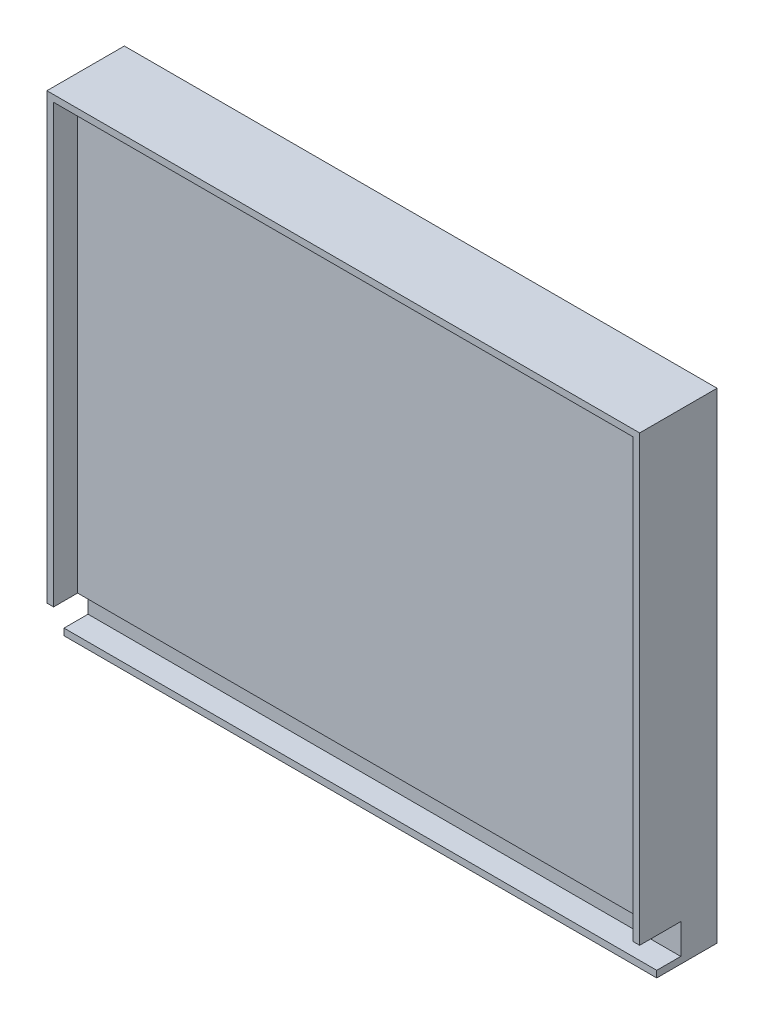
SolidWorks part; units mm, degrees
ref_plane "Front Plane" through (0, 0, 0) normal (0, 0, 1) x (1, 0, 0)
ref_plane "Top Plane" through (0, 0, 0) normal (0, 1, 0) x (1, 0, 0)
ref_plane "Right Plane" through (0, 0, 0) normal (1, 0, 0) x (0, 0, -1)
sketch "Sketch1" plane through (0, 0, 0) normal (0, 0, 1) x (1, 0, 0)
  line L1 (-68.3632, 130.6396) -> (213.5768, 130.6396)
  line L2 (-68.3632, 130.6396) -> (-68.3632, -97.9604)
  line L3 (-68.3632, -97.9604) -> (213.5768, -97.9604)
  line L4 (213.5768, 130.6396) -> (213.5768, -97.9604)
  dimension "D1" = 281.94
  dimension "D2" = 228.6
extrude "Boss-Extrude2" add sketch "Sketch1" along normal blind 25.4
sketch "Sketch3" plane through (0, 0, 25.4) normal (0, 0, 1) x (1, 0, 0)
  line L0 (-68.3632, -97.9604) -> (-68.3632, -80.4344)
  line L1 (-68.3632, 130.6396) -> (-68.3632, -97.9604) construction
  line L2 (-68.3632, -80.4344) -> (213.5768, -80.4344)
  line L3 (213.5768, -97.9604) -> (213.5768, 130.6396) construction
  line L4 (213.5768, -80.4344) -> (213.5768, -97.9604)
  line L5 (213.5768, -97.9604) -> (-68.3632, -97.9604)
  dimension "D1" = 17.526
extrude "Cut-Extrude1" cut sketch "Sketch3" against normal blind 8.128
sketch "Sketch4" plane through (-68.3632, 0, 0) normal (-1, 0, 0) x (0, 0, 1)
  line L0 (25.4, 130.6396) -> (36.83, 130.6396)
  line L1 (36.83, 130.6396) -> (36.83, -80.4344)
  line L2 (36.83, -80.4344) -> (25.4, -80.4344)
  line L3 (25.4, -80.4344) -> (25.4, 130.6396)
  dimension "D1" = 11.43
extrude "Boss-Extrude4" add sketch "Sketch4" against normal blind 3.175 separate body
sketch "Sketch5" plane through (0, 130.6396, 0) normal (0, 1, 0) x (1, 0, 0)
  line L15 (-65.1882, -36.83) -> (-65.1882, -25.4)
  line L16 (-65.1882, -25.4) -> (213.5768, -25.4)
  line L17 (213.5768, -25.4) -> (213.5768, -36.83)
  line L18 (213.5768, -36.83) -> (-65.1882, -36.83)
sketch "Sketch8" plane through (0, -97.9604, 0) normal (0, -1, 0) x (1, 0, 0)
  line L0 (-68.3632, 17.272) -> (-68.3632, 28.702)
  line L1 (-68.3632, 28.702) -> (213.5768, 28.702)
  line L2 (213.5768, 28.702) -> (213.5768, 17.272)
  line L3 (213.5768, 17.272) -> (-68.3632, 17.272)
  dimension "D1" = 11.43
extrude "Boss-Extrude9" add sketch "Sketch5" against normal blind 3.175
sketch "Sketch9" plane through (213.5768, 0, 0) normal (1, 0, 0) x (0, 0, -1)
  line L0 (-25.4, -80.4344) -> (-36.83, -80.4344)
  line L1 (-36.83, -80.4344) -> (-36.83, 127.4646)
  line L2 (-36.83, 127.4646) -> (-25.4, 127.4646)
  line L3 (-25.4, 127.4646) -> (-25.4, -80.4344)
  dimension "D1" = 11.43
extrude "Boss-Extrude10" add sketch "Sketch9" against normal blind 3.175
extrude "Boss-Extrude11" add sketch "Sketch8" against normal blind 3.175 separate body
combine bodies "Combine1" operation type add bodies to combine 115 114
